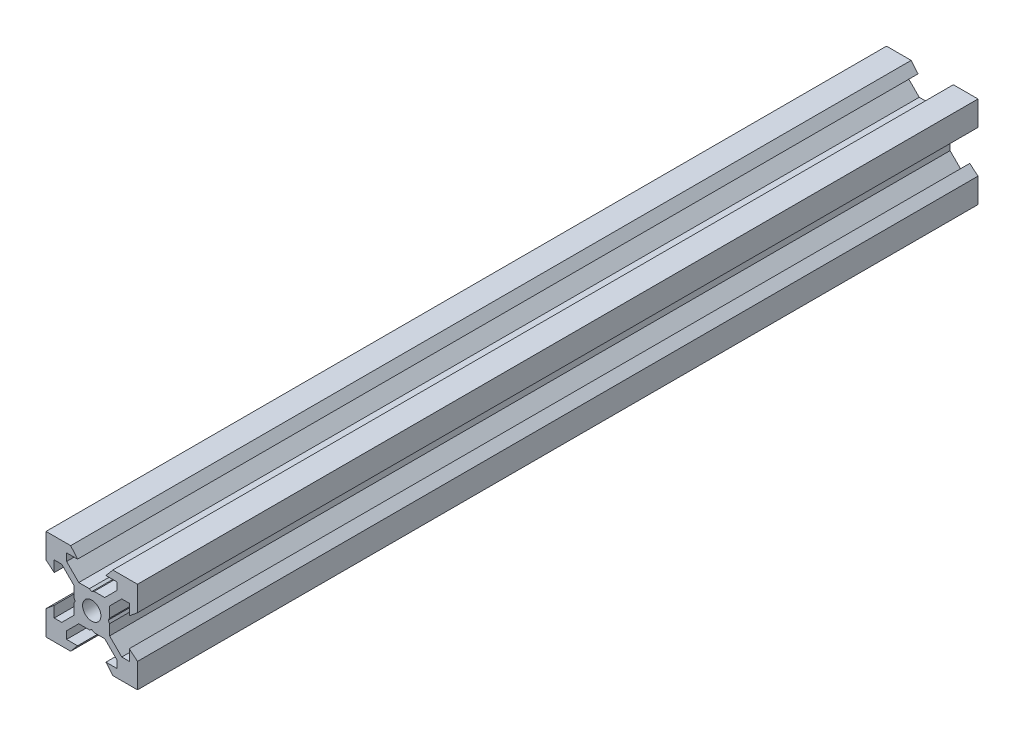
SolidWorks part; units mm, degrees
ref_plane "Front Plane" through (0, 0, 0) normal (0, 0, 1) x (1, 0, 0)
ref_plane "Top Plane" through (0, 0, 0) normal (0, 1, 0) x (1, 0, 0)
ref_plane "Right Plane" through (0, 0, 0) normal (1, 0, 0) x (0, 0, -1)
sketch "Sketch1" plane through (0, 0, 0) normal (0, 0, 1) x (1, 0, 0)
  line L0 (10, 10) -> (4.6104, 10) construction
  line L1 (10, 10) -> (10, 4.6104) construction
  line L2 (10, -10) -> (10, -4.6104) construction
  line L3 (10, -10) -> (4.6104, -10) construction
  line L4 (10, 10) -> (10, 4.6104)
  line L5 (6.5607, 5.5) -> (8.2, 5.5)
  line L6 (5.5, 8.2) -> (5.5, 6.5607)
  line L7 (10, 10) -> (4.6104, 10)
  line L8 (10, 10) -> (10, 4.6104)
  line L9 (6.5607, 5.5) -> (3.9, 2.8393)
  line L10 (5.5, 6.5607) -> (2.8393, 3.9)
  line L11 (10, 4.6104) -> (8.2, 3.1)
  line L12 (4.6104, 10) -> (3.1, 8.2)
  line L13 (8.2, 3.1) -> (8.2, 5.5)
  line L14 (3.1, 8.2) -> (5.5, 8.2)
  line L15 (-6.5607, 5.5) -> (-8.2, 5.5)
  line L16 (6.5607, -5.5) -> (8.2, -5.5)
  line L17 (3.1, -8.2) -> (5.5, -8.2)
  line L18 (8.2, -3.1) -> (8.2, -5.5)
  line L19 (4.6104, -10) -> (3.1, -8.2)
  line L20 (10, -4.6104) -> (8.2, -3.1)
  line L21 (0.5196, -3.9) -> (0, -3.6)
  line L22 (0.5196, 3.9) -> (0, 3.6)
  line L23 (3.6, 0) -> (3.9, -0.5196)
  line L24 (3.9, 0.5196) -> (3.6, 0)
  line L25 (3.9, 0.5196) -> (3.9, 2.8393)
  line L26 (2.8393, 3.9) -> (0.5196, 3.9)
  line L27 (3.9, -2.8393) -> (3.9, -0.5196)
  line L28 (2.8393, -3.9) -> (0.5196, -3.9)
  line L29 (5.5, -6.5607) -> (2.8393, -3.9)
  line L30 (6.5607, -5.5) -> (3.9, -2.8393)
  line L31 (10, -10) -> (10, -4.6104)
  line L32 (10, -10) -> (4.6104, -10)
  line L33 (5.5, -8.2) -> (5.5, -6.5607)
  line L34 (-6.5607, -5.5) -> (-8.2, -5.5)
  line L35 (10, -10) -> (10, -4.6104)
  line L36 (0, 0) -> (0, 8.2) construction
  line L37 (-10, -10) -> (-4.6104, -10) construction
  line L38 (-10, -10) -> (-10, -4.6104) construction
  line L39 (-10, 10) -> (-10, 4.6104) construction
  line L40 (-10, 10) -> (-4.6104, 10) construction
  line L41 (-10, -10) -> (-10, -4.6104)
  line L43 (-5.5, -8.2) -> (-5.5, -6.5607)
  line L44 (-10, -10) -> (-4.6104, -10)
  line L45 (-10, -10) -> (-10, -4.6104)
  line L46 (-6.5607, -5.5) -> (-3.9, -2.8393)
  line L47 (-5.5, -6.5607) -> (-2.8393, -3.9)
  line L48 (-2.8393, -3.9) -> (-0.5196, -3.9)
  line L49 (-3.9, -2.8393) -> (-3.9, -0.5196)
  line L50 (-2.8393, 3.9) -> (-0.5196, 3.9)
  line L51 (-3.9, 0.5196) -> (-3.9, 2.8393)
  line L52 (-3.9, 0.5196) -> (-3.6, 0)
  line L53 (-3.6, 0) -> (-3.9, -0.5196)
  line L54 (-0.5196, 3.9) -> (0, 3.6)
  line L55 (-0.5196, -3.9) -> (0, -3.6)
  line L56 (-10, -4.6104) -> (-8.2, -3.1)
  line L57 (-4.6104, -10) -> (-3.1, -8.2)
  line L58 (-8.2, -3.1) -> (-8.2, -5.5)
  line L59 (-3.1, -8.2) -> (-5.5, -8.2)
  line L60 (-10, -10) -> (10, -10) construction
  line L61 (-10, -10) -> (-10, 10) construction
  line L62 (-3.1, 8.2) -> (-5.5, 8.2)
  line L63 (-8.2, 3.1) -> (-8.2, 5.5)
  line L64 (-4.6104, 10) -> (-3.1, 8.2)
  line L65 (-10, 4.6104) -> (-8.2, 3.1)
  line L66 (-5.5, 6.5607) -> (-2.8393, 3.9)
  line L67 (-6.5607, 5.5) -> (-3.9, 2.8393)
  line L68 (-10, 10) -> (-10, 4.6104)
  line L69 (-10, 10) -> (-4.6104, 10)
  line L70 (-5.5, 8.2) -> (-5.5, 6.5607)
  line L71 (-10, 10) -> (10, 10) construction
  line L72 (-10, 10) -> (-10, 4.6104)
  line L73 (10, -10) -> (10, 10) construction
  line L74 (-10, -10) -> (10, 10) construction
  line L75 (-10, 10) -> (10, -10) construction
  circle A0 centre (0, 0) radius 2
  dimension "D7" = 4
  dimension "D1" = 20
  dimension "D2" = 5.3896
  dimension "D3" = 4.5
  dimension "D4" = 50
  dimension "D5" = 1.8
  dimension "D6" = 1.5104
  dimension "D8" = 5.5
  dimension "D9" = 120
  dimension "D10" = 0.3
  dimension "D11" = 2.3197
  dimension "D12" = 7.8
  dimension "D13" = 7.8
  dimension "D14" = 1.5
  dimension "D15" = 2.6607
extrude "Boss-Extrude1" add sketch "Sketch1" along normal mid plane 183.74 contours L70 L62 L64 L69 L68 L65 L63 L15 L67 L51 L52 L53 L49 L46 L34 L58 L56 L41 L44 L57 L59 L43 L47 L48 L55 L21 L28 L29 L33 L17 L19 L32 L31 L20 L18 L16 L30 L27 L23 L24 L25 L9 L5 L13 L11 L4 L7 L12 L14 L6 L10 region at (9.7172, 7.3052, 0)
